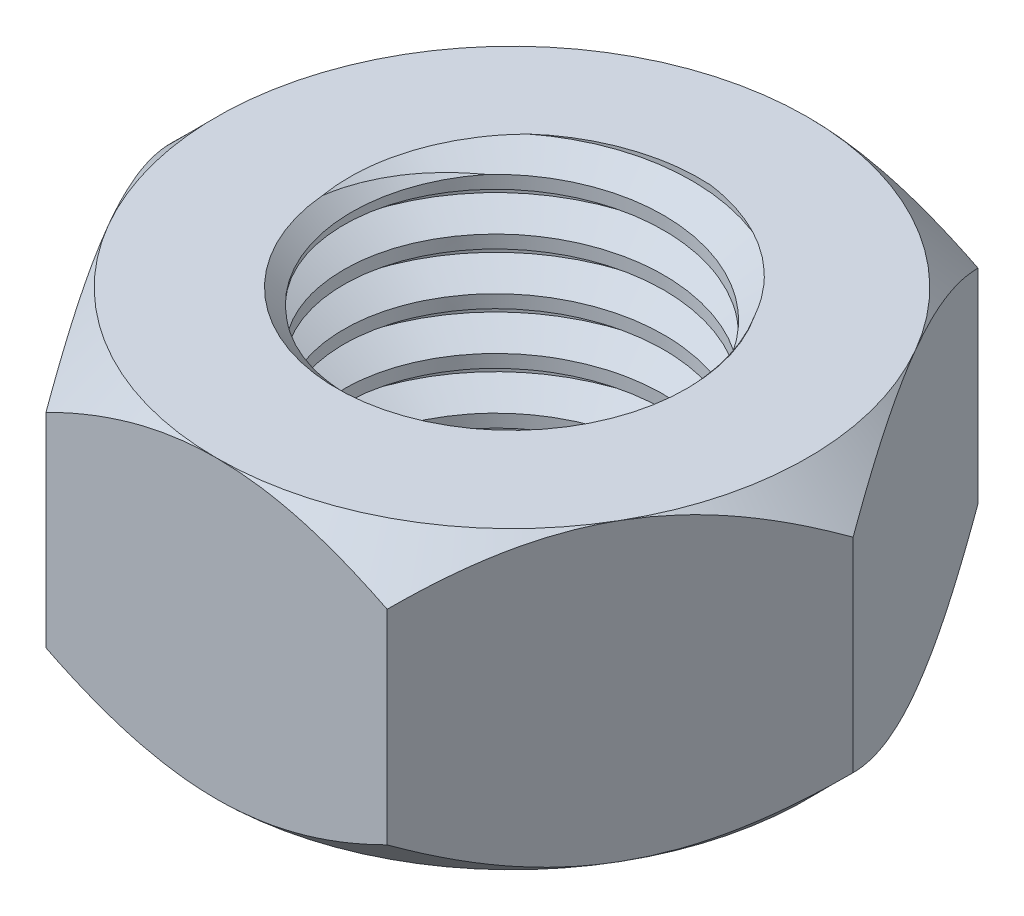
SolidWorks part; units mm, degrees
ref_plane "Front Plane" through (0, 0, 0) normal (0, 0, 1) x (1, 0, 0)
ref_plane "Top Plane" through (0, 0, 0) normal (0, 1, 0) x (1, 0, 0)
ref_plane "Right Plane" through (0, 0, 0) normal (1, 0, 0) x (0, 0, -1)
sketch "Sketch1" plane through (0, 0, 0) normal (0, 1, 0) x (1, 0, 0)
  line L1 (11.547, 0) -> (5.7735, 10)
  line L2 (5.7735, 10) -> (-5.7735, 10)
  line L3 (-5.7735, 10) -> (-11.547, 0)
  line L4 (-11.547, 0) -> (-5.7735, -10)
  line L5 (-5.7735, -10) -> (5.7735, -10)
  line L6 (5.7735, -10) -> (11.547, 0)
  circle A0 centre (0, 0) radius 10 construction
  dimension "D1" = 20
extrude "Boss-Extrude4" add sketch "Sketch1" along normal mid plane 10
sketch "Sketch4" plane through (0, 5, 0) normal (0, 1, 0) x (1, 0, 0)
  line L3 (-5.7735, -10) -> (5.7735, -10) construction
  circle A0 centre (0, 0) radius 10
extrude "Cut-Extrude2" cut sketch "Sketch4" against normal blind 10 draft 45 flip side to cut
mirror "Mirror2" about plane through (0, 0, 0) normal (0, 1, 0) of "Cut-Extrude2"
sketch "Sketch5" plane through (0, 5, 0) normal (0, 1, 0) x (1, 0, 0)
  circle A0 centre (0, 0) radius 5.425
  dimension "D1" = 10.85
extrude "Cut-Extrude3" cut sketch "Sketch5" against normal blind 10
chamfer "Chamfer1" distance 0.5 angle 45 2 edges at (0, -5, 5.425) (0, 5, 5.425)
thread "Thread1" pitch 1.75 start angle 0, offset 5, length 0, pitch 1.75, diameter 10.85
ref_plane "Plane1" through (-5.425, 9.5, 0) normal (0, 0, 1) x (-1, 0, 0)
sketch "Thread Profile1" plane through (-5.425, 9.5, 0) normal (0, 0, 1) x (-1, 0, 0)
  line L0 (0, 0) -> (0, 1.75) construction
  line L1 (0, 0) -> (0.9472, 0.5469)
  line L2 (0.9472, 0.5469) -> (0.9472, 0.7656)
  line L3 (0.9472, 0.7656) -> (0, 1.3125)
  line L4 (0.9472, 0.6562) -> (0, 0.6562) construction
  line L11 (0, 0) -> (0, 1.3125)
  point P2 (0, 0)
  dimension "Pitch" = 1.75
  dimension "Profile_Angle" = 60
  dimension "Profile_Land" = 0.2188
  dimension "Profile_Height" = 0.9472
